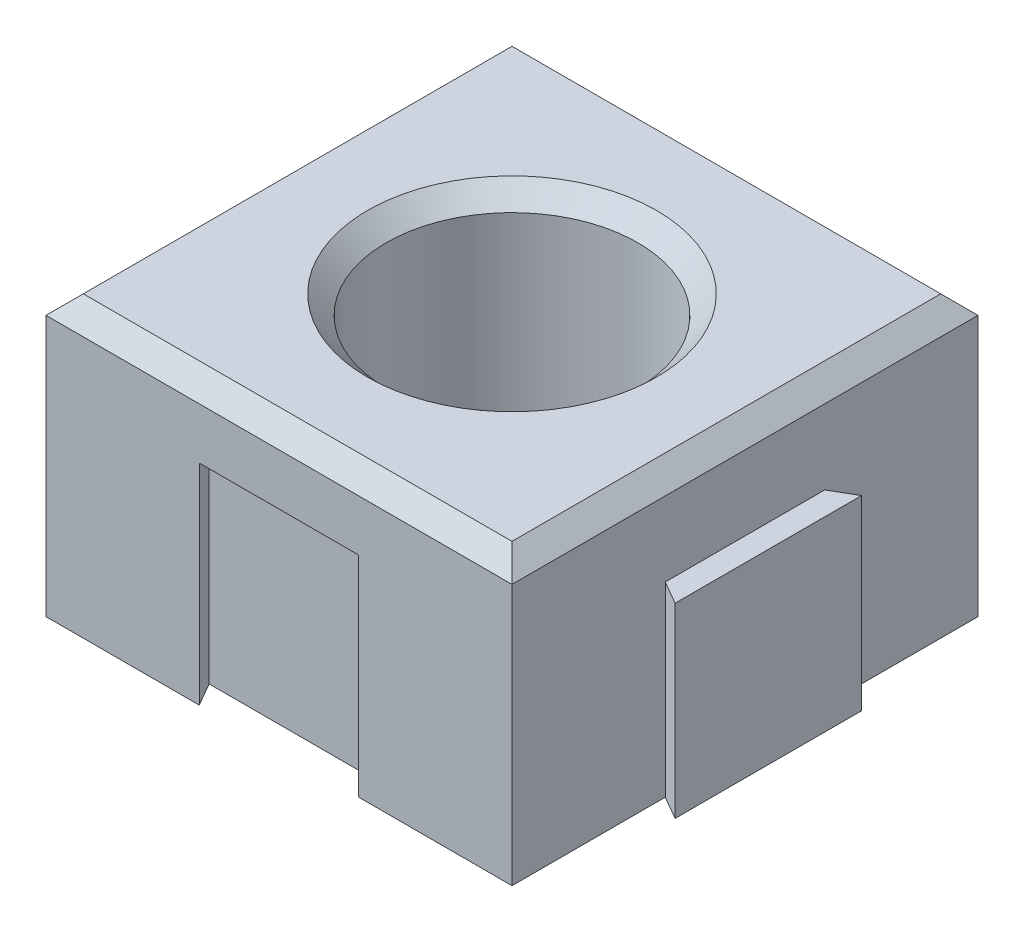
SolidWorks part; units mm, degrees
ref_plane "Front Plane" through (0, 0, 0) normal (0, 0, 1) x (1, 0, 0)
ref_plane "Top Plane" through (0, 0, 0) normal (0, 1, 0) x (1, 0, 0)
ref_plane "Right Plane" through (0, 0, 0) normal (1, 0, 0) x (0, 0, -1)
sketch "Sketch1" plane through (0, 0, 0) normal (0, 1, 0) x (1, 0, 0)
  line L1 (0, 0) -> (50, 0)
  line L2 (0, 0) -> (0, 50)
  line L3 (0, 50) -> (50, 50)
  line L4 (50, 0) -> (50, 50)
  dimension "D1" = 50
extrude "Boss-Extrude1" add sketch "Sketch1" along normal blind 30
sketch "Sketch2" plane through (0, 30, 0) normal (0, 1, 0) x (1, 0, 0)
  line L0 (0, 0) -> (50, 50) construction
  line L1 (0, 50) -> (50, 0) construction
  circle A0 centre (25, 25) radius 13.5
  dimension "D1" = 27
extrude "Cut-Extrude1" cut sketch "Sketch2" against normal blind 26
sketch "Sketch3" plane through (0, 0, 0) normal (0, 1, 0) x (1, 0, 0)
  line L0 (50, 33.5566) -> (52.5, 35)
  line L1 (50, 0) -> (50, 50) construction
  line L2 (52.5, 35) -> (52.5, 15)
  line L3 (52.5, 15) -> (50, 16.4434)
  line L4 (50, 25) -> (52.5, 25) construction
  line L5 (16.4434, 50) -> (15, 52.5)
  line L6 (50, 50) -> (0, 50) construction
  line L7 (15, 52.5) -> (35, 52.5)
  line L8 (35, 52.5) -> (33.5566, 50)
  line L9 (25, 52.5) -> (25, 50) construction
  line L10 (0, 33.5566) -> (2.5, 35)
  line L11 (0, 50) -> (0, 0) construction
  line L12 (2.5, 35) -> (2.5, 15)
  line L13 (2.5, 15) -> (0, 16.4434)
  line L14 (0, 25) -> (2.5, 25) construction
  line L15 (16.4434, 0) -> (15, 2.5)
  line L16 (0, 0) -> (50, 0) construction
  line L17 (15, 2.5) -> (35, 2.5)
  line L18 (35, 2.5) -> (33.5566, 0)
  line L19 (25, 0) -> (25, 2.5) construction
  line L20 (50, 16.4434) -> (50, 33.5566)
  line L21 (33.5566, 50) -> (16.4434, 50)
  line L22 (0, 33.5566) -> (0, 16.4434)
  line L23 (16.4434, 0) -> (33.5566, 0)
  point P8 (50, 25)
  dimension "D2" = 60
  dimension "D3" = 2.5
  dimension "D4" = 20
extrude "Boss-Extrude2" add sketch "Sketch3" along normal blind 20 contours L2 L3 L20 L0
extrude "Boss-Extrude3" add sketch "Sketch3<3>" along normal blind 20 contours L7 L8 L21 L5
sketch "Sketch3<3>" plane through (0, 0, 0) normal (0, 1, 0) x (1, 0, 0) same geometry as "Sketch3"
extrude "Cut-Extrude2" cut sketch "Sketch3<4>" along normal blind 20 contours L12 L13 L22 L10
sketch "Sketch3<4>" plane through (0, 0, 0) normal (0, 1, 0) x (1, 0, 0) same geometry as "Sketch3"
extrude "Cut-Extrude3" cut sketch "Sketch3<5>" along normal blind 20 contours L17 L18 L23 L15
sketch "Sketch3<5>" plane through (0, 0, 0) normal (0, 1, 0) x (1, 0, 0) same geometry as "Sketch3"
chamfer "Chamfer1" distance 2 angle 45 5 edges at (25, 30, -50) (50, 30, -25) (25, 30, 0) (0, 30, -25) (25, 30, -11.5)
sketch "Sketch4" plane through (0, 0, 0) normal (0, 1, 0) x (1, 0, 0)
  line L0 (12.5, 12.5) -> (37.5, 37.5) construction
  line L1 (12.5, 12.5) -> (37.5, 12.5) construction
  line L2 (12.5, 12.5) -> (12.5, 37.5) construction
  line L3 (12.5, 37.5) -> (37.5, 37.5) construction
  line L4 (37.5, 12.5) -> (37.5, 37.5) construction
  line L5 (12.5, 37.5) -> (37.5, 12.5) construction
  line L6 (0, 0) -> (12.5, 12.5) construction
  line L7 (12.5, 37.5) -> (0, 50) construction
  line L8 (50, 50) -> (37.5, 37.5) construction
  line L9 (50, 0) -> (37.5, 12.5) construction
  line L10 (0, 25) -> (25, 25) construction
  circle A0 centre (12.5, 37.5) radius 3.1
  circle A1 centre (37.5, 37.5) radius 3.1
  circle A2 centre (37.5, 12.5) radius 3.1
  circle A3 centre (12.5, 12.5) radius 3.1
  point P15 (12.5, 25)
  dimension "D1" = 6.2
extrude "Cut-Extrude4" cut sketch "Sketch4" along normal blind 2.5
chamfer "Chamfer2" distance 1 angle 45 4 edges at (37.5, 2.5, -9.4) (12.5, 2.5, -9.4) (12.5, 2.5, -34.4) (37.5, 2.5, -34.4)
chamfer "Chamfer3" distance 2.5 angle 45 2 edges at (0, 20, -25) (25, 20, 0)
